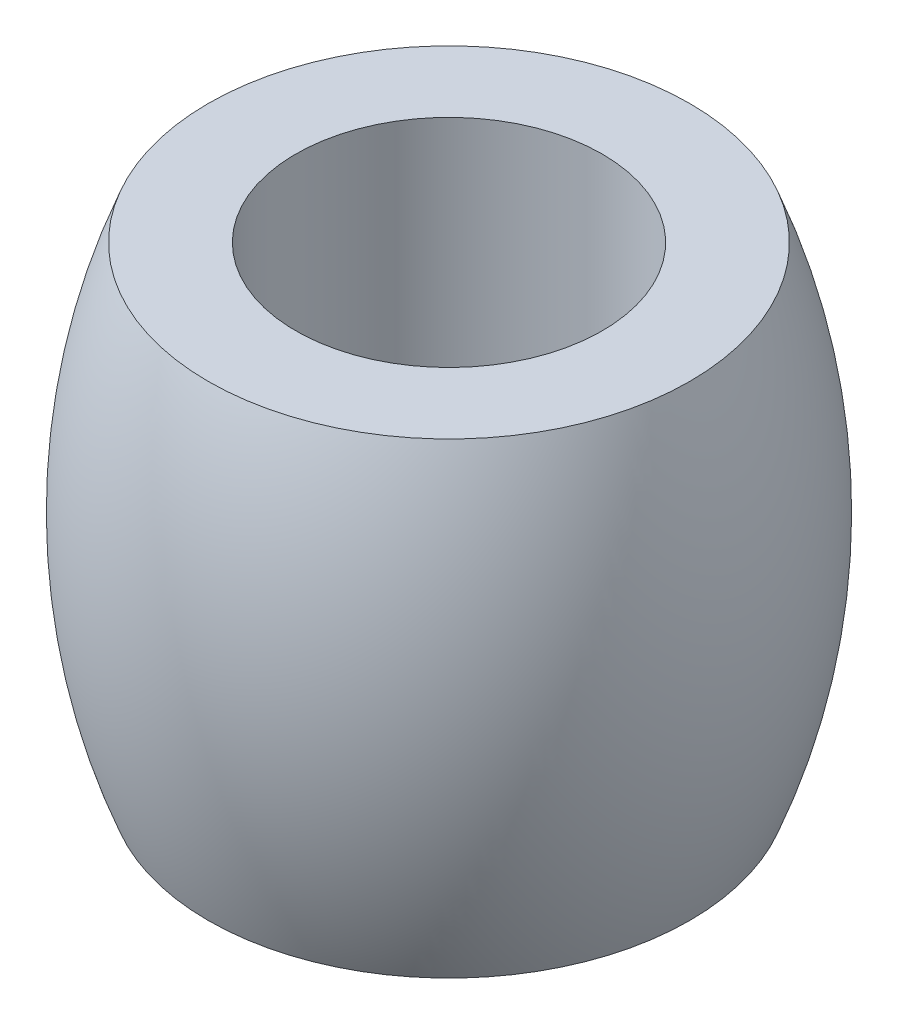
SolidWorks part; units mm, degrees
ref_plane "Płaszczyzna przednia" through (0, 0, 0) normal (0, 0, 1) x (1, 0, 0)
ref_plane "Płaszczyzna górna" through (0, 0, 0) normal (0, 1, 0) x (1, 0, 0)
ref_plane "Płaszczyzna prawa" through (0, 0, 0) normal (1, 0, 0) x (0, 0, -1)
sketch "Sketch1" plane through (0, 0, 0) normal (0, 0, 1) x (1, 0, 0)
  line L0 (0, 0) -> (0, 11.3433) construction
  line L1 (-5.25, 16) -> (-5.25, 0)
  line L2 (-5.25, 0) -> (-8.25, 0)
  line L3 (-5.25, 16) -> (-8.25, 16)
  line L4 (-10, 11.3433) -> (-10, 0) construction
  arc A0 (-8.25, 0) -> (-8.25, 16) centre (12.2439, 8) cw
  dimension "D2" = 10
  dimension "D5" = 22
  dimension "D1" = 5.25
  dimension "D3" = 3
  dimension "D4" = 3
  dimension "D6" = 16
revolve "Revolve1" add sketch "Sketch1" angle 360 about L0
